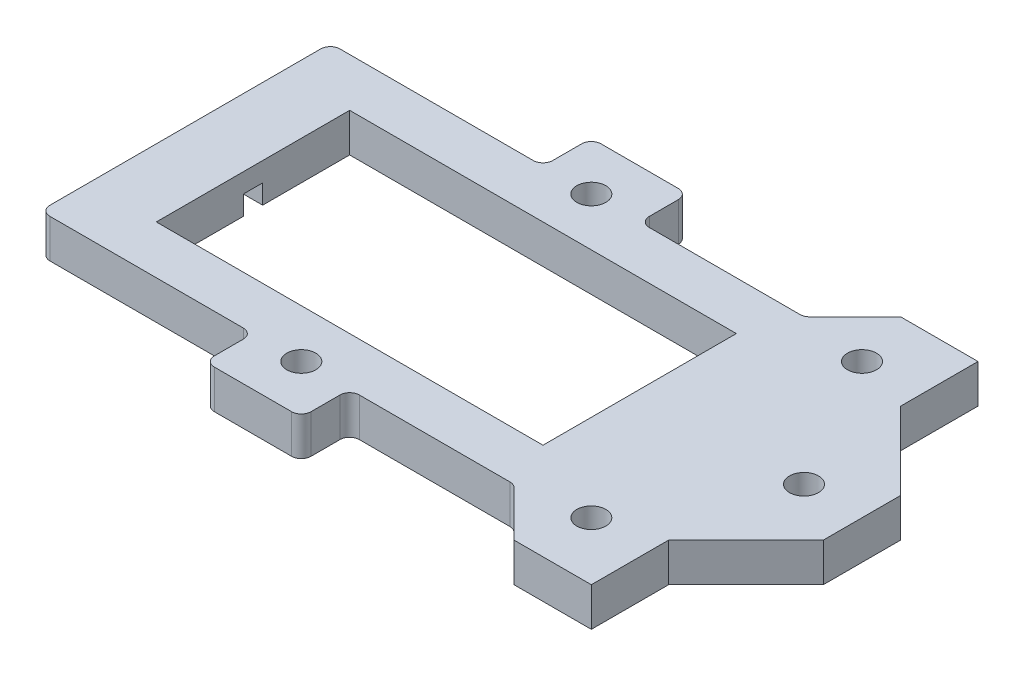
SolidWorks part; units mm, degrees
material "ABS"
ref_plane "前视基准面" through (0, 0, 0) normal (0, 0, 1) x (1, 0, 0)
ref_plane "上视基准面" through (0, 0, 0) normal (0, 1, 0) x (1, 0, 0)
ref_plane "右视基准面" through (0, 0, 0) normal (1, 0, 0) x (0, 0, -1)
sketch "草图1" plane through (0, 0, 0) normal (0, 1, 0) x (1, 0, 0)
  line L0 (-41.6626, 0) -> (45.9673, 0) construction
  line L1 (-27, -15) -> (27, -15)
  line L2 (-27, -15) -> (-27, 15)
  line L3 (-27, 15) -> (27, 15)
  line L4 (27, -15) -> (27, 15)
  line L5 (-27, -15) -> (27, 15) construction
  line L6 (-27, 15) -> (27, -15) construction
  line L7 (22, 15) -> (27, 20)
  line L8 (-20, -10) -> (20, -10)
  line L9 (-20, -10) -> (-20, 10)
  line L10 (-20, 10) -> (20, 10)
  line L11 (20, -10) -> (20, 10)
  line L12 (-20, -10) -> (20, 10) construction
  line L13 (-20, 10) -> (20, -10) construction
  line L14 (27, 20) -> (35, 20)
  line L15 (35, 20) -> (35, 12)
  line L16 (35, 12) -> (43, 4)
  line L17 (43, 4) -> (43, -4)
  line L18 (35, -12) -> (43, -4)
  line L19 (35, -20) -> (35, -12)
  line L20 (27, -20) -> (35, -20)
  line L21 (22, -15) -> (27, -20)
  line L22 (0, 27.0049) -> (0, -28.8727) construction
  line L23 (-5, 15) -> (-5, 20)
  line L24 (-5, 20) -> (5, 20)
  line L25 (5, 20) -> (5, 15)
  line L26 (5, -20) -> (5, -15)
  line L27 (-5, -20) -> (5, -20)
  line L28 (-5, -15) -> (-5, -20)
  point P0 (0, 0)
  point P8 (0, 0)
  point P20 (43, 0)
  dimension "D1" = 54
  dimension "D2" = 30
  dimension "D3" = 40
  dimension "D4" = 20
  dimension "D5" = 7
  dimension "D6" = 5
  dimension "D7" = 8
  dimension "D8" = 8
  dimension "D9" = 16
  dimension "D10" = 4
  dimension "D11" = 5
  dimension "D12" = 10
  dimension "D13" = 5
extrude "凸台-拉伸1" add sketch "草图1" along normal blind 4 contours L1 L4 L3 L2 L11 L8 L9 L10 | L25 L24 L23 L3 | L1 L28 L27 L26 | L1 L21 L20 L19 L18 L17 L16 L15 L14 L7 L3 L4 region at (-26.3823, 0, 0) region at (0, 0, 17.5) region at (0, 0, -17.5) region at (32.685, 0, 0)
sketch "草图2" plane through (0, 4, 0) normal (0, 1, 0) x (1, 0, 0)
  line L0 (-27, 15) -> (-5, 15) construction
  line L1 (35, 20) -> (35, 12) construction
  line L3 (-30.0206, 0) -> (47.4878, 0) construction
  line L4 (27, 20) -> (35, 20) construction
  line L5 (43, 4) -> (43, -4) construction
  circle A0 centre (0, 15) radius 1.5
  circle A1 centre (0, -15) radius 1.5
  circle A2 centre (29, 14) radius 1.5
  circle A3 centre (29, -14) radius 1.5
  circle A4 centre (37, 0) radius 1.5
  dimension "D1" = 3
  dimension "D2" = 3
  dimension "D5" = 3
  dimension "D3" = 6
  dimension "D4" = 6
  dimension "D6" = 6
extrude "切除-拉伸1" cut sketch "草图2" against normal through all
sketch "草图3" plane through (0, 0, 0) normal (0, -1, 0) x (1, 0, 0)
  line L0 (-31.9776, 0) -> (47.5651, 0) construction
  line L1 (-27, 1) -> (-20, 1)
  line L2 (-27, 15) -> (-27, -15) construction
  line L3 (-20, 10) -> (-20, -10) construction
  line L4 (-20, 1) -> (-20, -1)
  line L5 (-20, -1) -> (-27, -1)
  line L6 (-27, -1) -> (-27, 1)
  line L7 (20, 1) -> (27, 1)
  line L8 (20, 10) -> (20, -10) construction
  line L9 (27, 1) -> (27, -1)
  line L10 (27, -1) -> (20, -1)
  line L11 (20, -1) -> (20, 1)
  dimension "D1" = 2
  dimension "D2" = 7
extrude "切除-拉伸2" cut sketch "草图3" against normal blind 2
fillet "圆角1" radius 1 12 edges at (-5, 2, -15) (-5, 2, -20) (5, 2, -20) (5, 2, -15) (22, 2, -15) (22, 2, 15) (5, 2, 15) (5, 2, 20) (-5, 2, 20) (-5, 2, 15) (-27, 2, 15) (-27, 2, -15)
